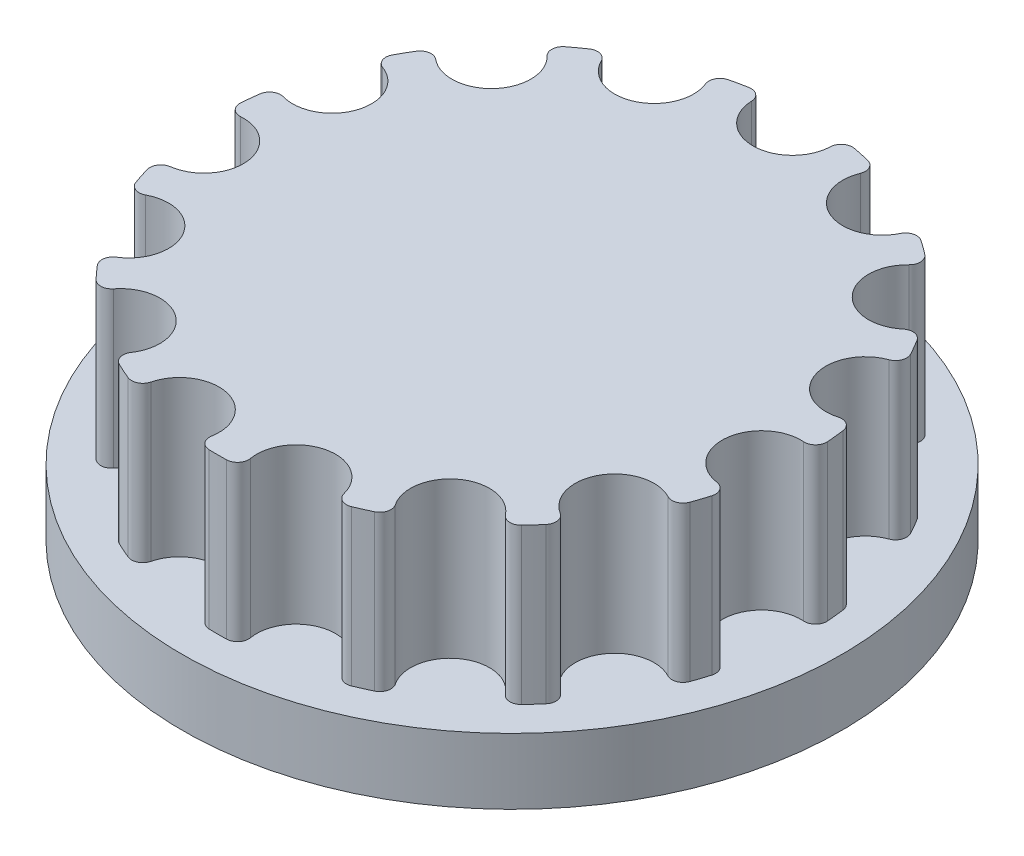
SolidWorks part; units mm, degrees
ref_plane "Front Plane" through (0, 0, 0) normal (0, 0, 1) x (1, 0, 0)
ref_plane "Top Plane" through (0, 0, 0) normal (0, 1, 0) x (1, 0, 0)
ref_plane "Right Plane" through (0, 0, 0) normal (1, 0, 0) x (0, 0, -1)
sketch "Sketch1" plane through (0, 0, 0) normal (0, 1, 0) x (1, 0, 0)
  line L0 (0, 0) -> (0, 11.3652) construction
  line L1 (0, 0) -> (4.405, 9.8939) construction
  circle A0 centre (0, 0) radius 11.3652 construction
  circle A1 centre (0, 0) radius 9.3052 construction
  circle A2 centre (0, 10.8302) radius 1.525 construction
  circle A5 centre (4.405, 9.8939) radius 1.525 construction
  arc A6 (0, 9.3052) -> (1.524, 10.7749) centre (0, 10.8302) ccw
  arc A7 (1.524, 10.7749) -> (2.0305, 11.1823) centre (1.9537, 10.7593) cw
  arc A8 (2.6933, 11.0415) -> (2.9903, 10.4632) centre (2.5914, 10.6237) cw
  arc A9 (3.7848, 8.5007) -> (2.9903, 10.4632) centre (4.405, 9.8939) cw
  arc A10 (2.0305, 11.1823) -> (2.6933, 11.0415) centre (0, 0) cw
  arc A11 (0, 9.3052) -> (3.7848, 8.5007) centre (0, 0) ccw
  dimension "D1" = 22.7304
  dimension "D3" = 3.05
  dimension "D4" = 0.43
  dimension "D2" = 2.06
  dimension "D5" = 24
extrude "Boss-Extrude1" add sketch "Sketch1" along normal mid plane 6
ref_axis "Axis1" through (0, 3.3, 0) along (0, -1, 0)
pattern_circular "CirPattern1" count 15 over 360 about axis through (0, 3.3, 0) along (0, -1, 0) of "Boss-Extrude1"
sketch "Sketch2" plane through (0, -3, 0) normal (0, -1, 0) x (1, 0, 0)
  circle A0 centre (0, 0) radius 12.7304
  dimension "D1" = 25.4609
extrude "Boss-Extrude2" add sketch "Sketch2" along normal blind 2.54
mirror "Mirror1" [suppressed] about plane through (0, 0, 0) normal (0, 1, 0)
equation "\"TEETH_NUM\"= 15"
equation "\"TOOTH_PITCH\"= 5mm"
equation "\"PITCH_LINE_OFFSET\"= .5715mm"
equation "\"DIAMETER_PER_GROOVE\"= 1.59156mm"
equation "\"PITCH_DIAMETER\"= \"TEETH_NUM\" * \"DIAMETER_PER_GROOVE\""
equation "\"OUTSIDE_DIAMETER\"= \"PITCH_DIAMETER\" - \"PITCH_LINE_OFFSET\" * 2"
equation "\"D1@Sketch1\"=\"OUTSIDE_DIAMETER\""
equation "\"TOOTH_HEIGHT\"= 2.06mm"
equation "\"D2@Sketch1\"=\"TOOTH_HEIGHT\""
equation "\"TOOTH_DIAMETER\"= 3.05mm"
equation "\"INTERNAL_RADIUS\"= .43mm"
equation "\"D3@Sketch1\"=\"TOOTH_DIAMETER\""
equation "\"D5@Sketch1\"=360 / \"TEETH_NUM\""
equation "\"D4@Sketch1\"=\"INTERNAL_RADIUS\""
equation "\"D1@CirPattern1\"=\"TEETH_NUM\""
equation "\"D1@Sketch2\"=\"PITCH_DIAMETER\"+1/16"
